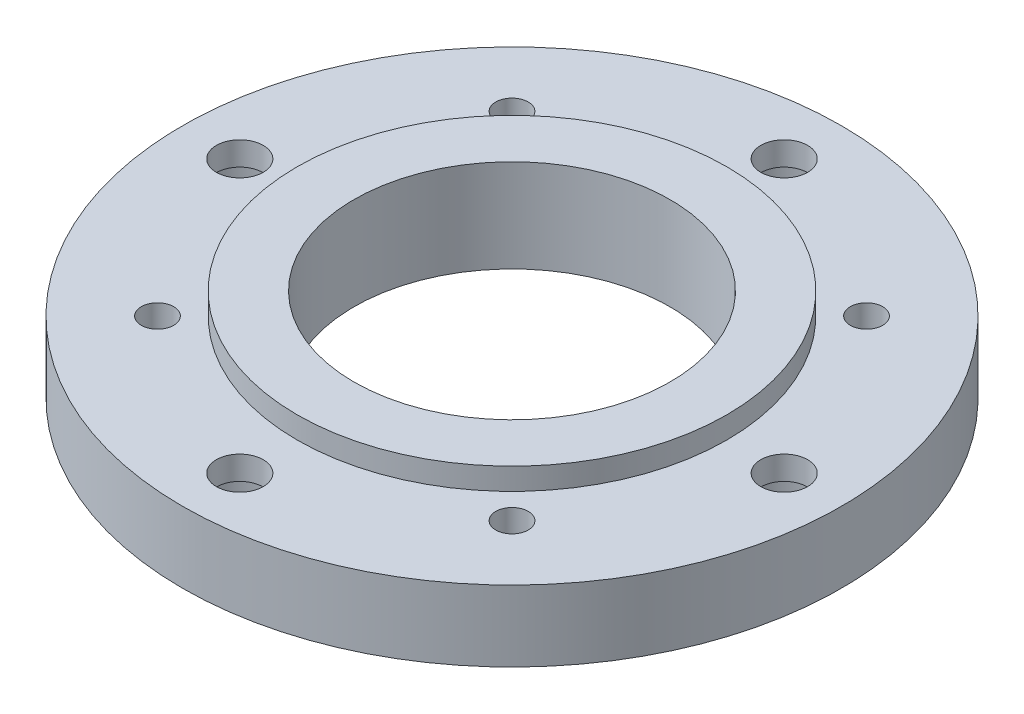
SolidWorks part; units mm, degrees
ref_plane "Front Plane" through (0, 0, 0) normal (0, 0, 1) x (1, 0, 0)
ref_plane "Top Plane" through (0, 0, 0) normal (0, 1, 0) x (1, 0, 0)
ref_plane "Right Plane" through (0, 0, 0) normal (1, 0, 0) x (0, 0, -1)
sketch "Sketch1" plane through (0, 0, 0) normal (0, 1, 0) x (1, 0, 0)
  line L0 (0, 18.9865) -> (0, 0) construction
  line L1 (0, 0) -> (12.3648, 12.3648) construction
  line L2 (-12.3648, 12.3648) -> (0, 0) construction
  line L3 (0, 0) -> (12.3648, -12.3648) construction
  line L4 (0, 0) -> (-12.3648, -12.3648) construction
  circle A0 centre (0, 0) radius 22.987
  circle A1 centre (0, 0) radius 11.0236
  circle A2 centre (0, 0) radius 14.986
  circle A3 centre (0, 0) radius 18.9865 construction
  circle A4 centre (0, 0) radius 17.4865 construction
  circle A5 centre (-12.3648, 12.3648) radius 1.42 construction
  point P6 (0, 18.9865)
  point P7 (18.9865, 0)
  point P8 (0, -18.9865)
  point P9 (-18.9865, 0)
  point P11 (12.3648, 12.3648)
  point P12 (-12.3648, 12.3648)
  point P13 (-12.3648, -12.3648)
  point P14 (12.3648, -12.3648)
  point P21 (0, 0)
  dimension "D1" = 45.974
  dimension "D2" = 22.0472
  dimension "D3" = 29.972
  dimension "D8" = 2.84
  dimension "D4" = 8.001
  dimension "D5" = 4.0005
  dimension "D6" = 45
  dimension "D7" = 45
  dimension "D9" = 1.5
extrude "Boss-Extrude1" add sketch "Sketch1" along normal blind 4.953 contours A0 A2 | A2 A1 region at (-22.3368, 0, 0) region at (-14.5621, 0, 0)
extrude "Boss-Extrude2" add sketch "Sketch1<3>" along normal blind 6.477 contours A2 A1 region at (-14.5621, 0, 0)
sketch "Sketch1<3>" plane through (0, 0, 0) normal (0, 1, 0) x (1, 0, 0) same geometry as "Sketch1"
hole_wizard "#4-40 Tapped Hole1" positions "3DSketch1" profile "Sketch2" tap size "#4-40" standard "ANSI Inch" end condition through all
sketch3d "3DSketch1"
  point P0 (-12.3648, 4.953, -12.3648)
  point P2 (12.3648, 4.953, -12.3648)
  point P4 (12.3648, 4.953, 12.3648)
  point P6 (-12.3648, 4.953, 12.3648)
  point P10 (0, 0, 0)
  point P12 (0, 0, 0)
  point P14 (0, 0, 0)
sketch "Sketch2" plane through (-12.3648, 4.953, -12.3648) normal (1, 0, 0) x (0, 0, 1)
  line L0 (0, 0) -> (0, 4.953)
  line L1 (0, 4.953) -> (1.1303, 4.953)
  line L2 (1.1303, 4.953) -> (1.1303, 0)
  line L5 (1.1303, 0) -> (0, 0)
  line L11 (0, -6.35) -> (0, 107.95) construction
  dimension "Thru Tap Drill Dia." = 2.2606
  dimension "Thru Tap Drill Depth" = 4.953
cosmetic thread "Hole Thread1"
cosmetic thread "Hole Thread2"
cosmetic thread "Hole Thread3"
cosmetic thread "Hole Thread4"
hole_wizard "CBORE for #4 Binding Head Machine Screw1" positions "3DSketch2" profile "Sketch3" counterbore size "#4" standard "ANSI Inch" end condition through all
sketch3d "3DSketch2"
  point P0 (0, 0, -18.9865)
  point P3 (-18.9865, 0, 0)
  point P6 (0, 0, 18.9865)
  point P9 (18.9865, 0, 0)
  point P14 (0, 0, 0)
  point P15 (0, 0, 0)
  point P16 (0, 0, 0)
  point P17 (0, 0, 0)
sketch "Sketch3" plane through (0, 0, -18.9865) normal (1, 0, 0) x (0, 0, -1)
  line L0 (0, 0) -> (0, 6.477)
  line L1 (0, 6.477) -> (1.6319, 6.477)
  line L3 (1.6319, 6.477) -> (1.6319, 3.302)
  line L4 (1.6319, 3.302) -> (3.3731, 3.302)
  line L5 (3.3731, 3.302) -> (3.3731, 0)
  line L7 (3.3731, 0) -> (0, 0)
  line L11 (0, -6.35) -> (0, 107.95) construction
  dimension "Thru Hole Dia." = 3.2639
  dimension "Thru Hole Depth" = 6.477
  dimension "C'Bore Dia." = 6.7462
  dimension "C'Bore Depth" = 3.302
equation "\"D5@Sketch1\"=(\"D4@Sketch1\"/2)"
